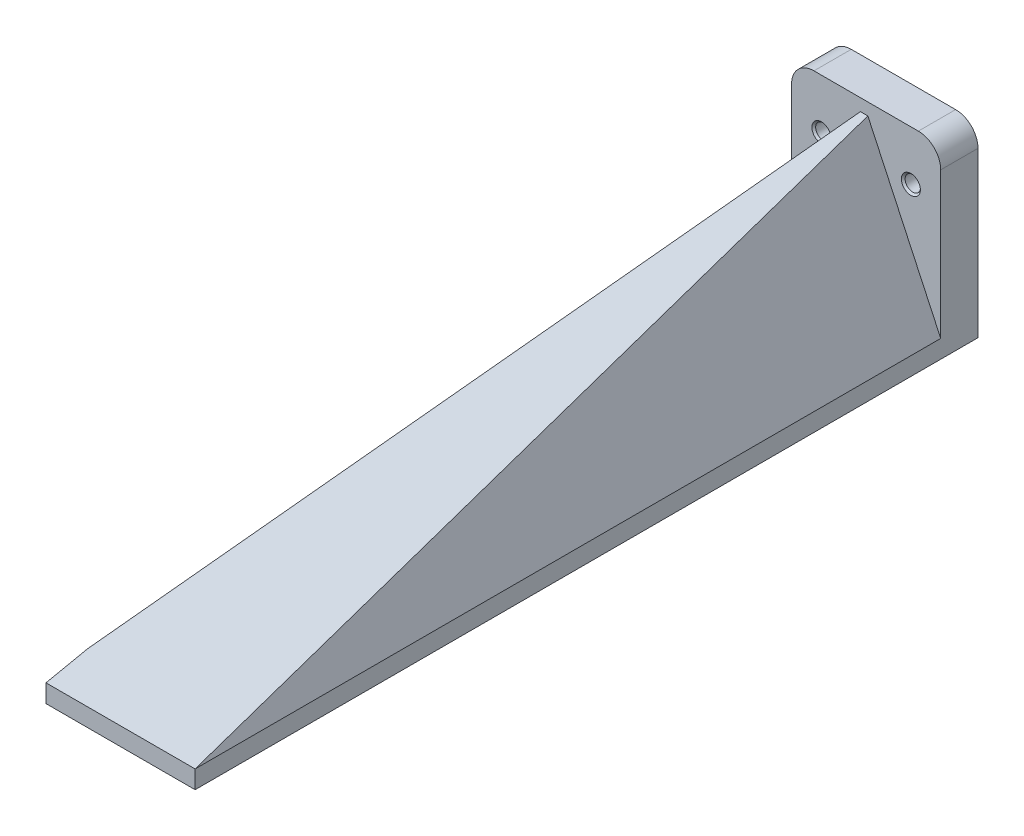
SolidWorks part; units mm, degrees
ref_plane "Front Plane" through (0, 0, 0) normal (0, 0, 1) x (1, 0, 0)
ref_plane "Top Plane" through (0, 0, 0) normal (0, 1, 0) x (1, 0, 0)
ref_plane "Right Plane" through (0, 0, 0) normal (1, 0, 0) x (0, 0, -1)
sketch "Sketch1" plane through (0, 0, 0) normal (0, 0, 1) x (1, 0, 0)
  line L1 (0, 0) -> (20, 0)
  line L2 (0, 0) -> (0, 25)
  line L3 (0, 25) -> (20, 25)
  line L4 (20, 0) -> (20, 25)
  dimension "D1" = 20
  dimension "D2" = 25
extrude "Boss-Extrude1" add sketch "Sketch1" along normal blind 5
sketch "Sketch2" plane through (0, 0, 5) normal (0, 0, 1) x (1, 0, 0)
  line L0 (0, 0) -> (0, 3.5874)
  line L1 (0, 25) -> (0, 0) construction
  line L2 (0, 3.5874) -> (9.2274, 23.3756)
  line L3 (9.2274, 23.3756) -> (10.2274, 23.3756)
  line L4 (10.2274, 23.3756) -> (20, 2.4183)
  line L5 (20, 0) -> (20, 25) construction
  line L6 (20, 2.4183) -> (20, 0)
  line L7 (20, 0) -> (0, 0)
  dimension "D1" = 155
  dimension "D2" = 155
  dimension "D3" = 1
extrude "Boss-Extrude3" add sketch "Sketch2" along normal blind 100
sketch "Sketch3" plane through (20, 0, 0) normal (1, 0, 0) x (0, 0, -1)
  line L0 (-105, 2.4183) -> (-5, 23.3756)
  line L1 (-5, 23.3756) -> (-105, 23.3756)
  line L2 (-105, 23.3756) -> (-105, 2.4183)
extrude "Cut-Extrude2" cut sketch "Sketch3" against normal through all
fillet "Fillet1" radius 3 2 edges at (0, 25, 2.5) (20, 25, 2.5)
shell "Shell1" thickness 2.5 removed face at (10, 0, 52.5)
hole_wizard "M2.5x0.45 Tapped Hole2" positions "Sketch8" profile "Sketch9" tap size "M2.5x0.45" standard "ANSI Metric" end condition through all
sketch "Sketch8" plane through (0, 0, 5) normal (0, 0, 1) x (1, 0, 0)
  line L0 (20, 2.4183) -> (20, 22) construction
  line L1 (0, 22) -> (0, 3.5874) construction
  point P0 (16, 18.3072)
  point P2 (4, 18.3072)
  dimension "D1" = 4
  dimension "D2" = 4
sketch "Sketch9" plane through (16, 18.3072, 5) normal (1, 0, 0) x (0, -1, 0)
  line L0 (0, 0) -> (0, 5)
  line L1 (0, 5) -> (1.025, 5)
  line L2 (1.025, 5) -> (1.025, 0.25)
  line L3 (1.025, 0.25) -> (1.275, 0)
  line L5 (1.275, 0) -> (0, 0)
  line L6 (-1.025, 0.25) -> (-1.275, 0) construction
  line L11 (0, -6.35) -> (0, 107.95) construction
  dimension "Thru Tap Drill Dia." = 2.05
  dimension "Thru Tap Drill Depth" = 5
  dimension "Near C'Sink Dia." = 2.55
  dimension "Near C'Sink Angle" = 90
cosmetic thread "Hole Thread5" parameters "D2"=2.5
cosmetic thread "Hole Thread6" parameters "D2"=2.5
